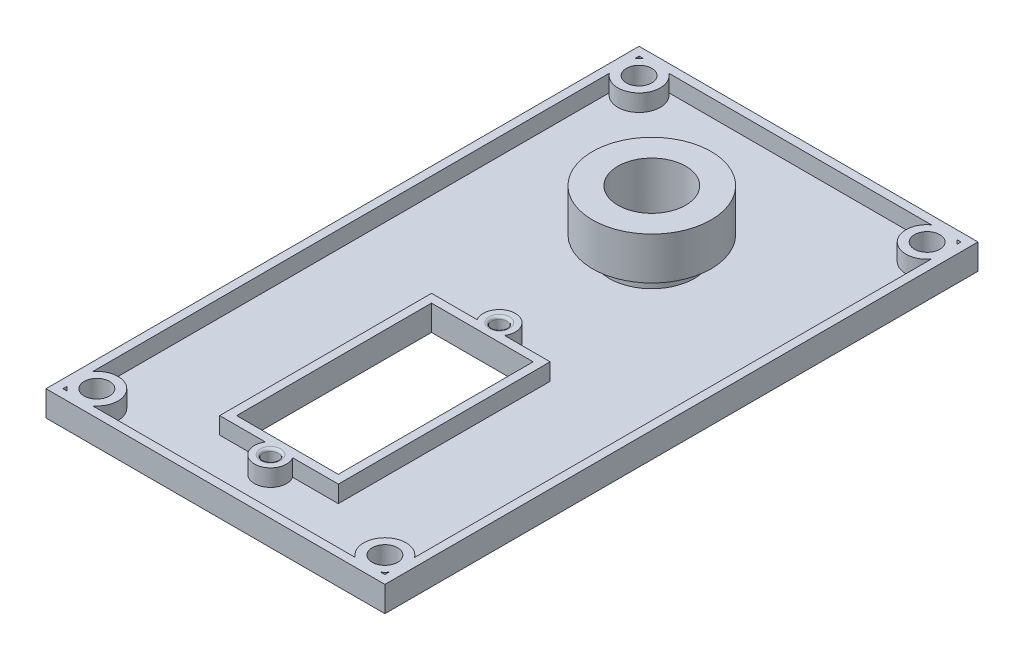
SolidWorks part; units mm, degrees
ref_plane "前视基准面" through (0, 0, 0) normal (0, 0, 1) x (1, 0, 0)
ref_plane "上视基准面" through (0, 0, 0) normal (0, 1, 0) x (1, 0, 0)
ref_plane "右视基准面" through (0, 0, 0) normal (1, 0, 0) x (0, 0, -1)
other "Configuration Table"
sketch "草图1" plane through (0, 0, 0) normal (0, 1, 0) x (1, 0, 0)
  line L0 (0, 38.6555) -> (0, -40.8509) construction
  line L1 (-20, 35) -> (20, 35)
  line L2 (-20, 35) -> (-20, -35)
  line L3 (-20, -35) -> (20, -35)
  line L4 (20, 35) -> (20, -35)
  line L5 (-20, 35) -> (20, -35) construction
  line L6 (-20, -35) -> (20, 35) construction
  line L8 (-6, -3.5) -> (6, -3.5)
  line L9 (-6, -3.5) -> (-6, -26.5)
  line L10 (-6, -26.5) -> (6, -26.5)
  line L11 (6, -3.5) -> (6, -26.5)
  line L12 (-6, -3.5) -> (6, -26.5) construction
  line L13 (-6, -26.5) -> (6, -3.5) construction
  point P0 (0, 0)
  point P8 (0, -15)
  dimension "D1" = 40
  dimension "D2" = 70
  dimension "D3" = 23
  dimension "D4" = 12
  dimension "D5" = 15
extrude "凸台-拉伸1" add sketch "草图1" along normal blind 3
sketch "草图2" plane through (0, 3, 0) normal (0, 1, 0) x (1, 0, 0)
  line L0 (0, 41.1406) -> (0, -42.4904) construction
  line L1 (-6, -26.5) -> (6, -26.5) construction
  line L2 (6, -3.5) -> (-6, -3.5) construction
  line L4 (20, -35) -> (20, 35)
  line L5 (20, 35) -> (-20, 35)
  line L6 (-20, 35) -> (-20, -35)
  line L7 (-20, -35) -> (20, -35)
  line L8 (20, -35) -> (20, 35)
  line L9 (20, 35) -> (-20, 35)
  line L10 (-20, 35) -> (-20, -35)
  line L11 (-20, -35) -> (20, -35)
  circle A0 centre (0, -28.5) radius 0.9
  circle A1 centre (0, -1.5) radius 0.9
  dimension "D2" = 1.8
  dimension "D3" = 1.8
  dimension "D4" = 2
  dimension "D5" = 2
  dimension "D1" = 0
extrude "切除-拉伸1" cut sketch "草图2" against normal blind 3 contours A0 | A1
sketch "草图3" plane through (0, 3, 0) normal (0, 1, 0) x (1, 0, 0)
  line L4 (20, -35) -> (20, 35)
  line L5 (20, 35) -> (-20, 35)
  line L6 (-20, 35) -> (-20, -35)
  line L7 (-20, -35) -> (20, -35)
  line L8 (20, -35) -> (20, 35)
  line L9 (20, 35) -> (-20, 35)
  line L10 (-20, 35) -> (-20, -35)
  line L11 (-20, -35) -> (20, -35)
  circle A0 centre (-17, -32) radius 1.5
  circle A1 centre (17, -32) radius 1.5
  circle A2 centre (17, 32) radius 1.5
  circle A3 centre (-17, 32) radius 1.5
  dimension "D2" = 3
  dimension "D3" = 3
  dimension "D4" = 3
  dimension "D5" = 3
  dimension "D6" = 3
  dimension "D7" = 3
  dimension "D8" = 3
  dimension "D9" = 3
  dimension "D10" = 3
  dimension "D11" = 3
  dimension "D12" = 3
  dimension "D13" = 3
  dimension "D1" = 0
extrude "切除-拉伸2" cut sketch "草图3" against normal through all contours A3 | A2 | A0 | A1 region at (-17, 3, 32) region at (17, 3, -32) region at (-17, 3, -32)
chamfer "倒角1" distance 0.5 angle 45 4 edges at (-17, 0, -30.5) (-17, 0, 33.5) (17, 0, 33.5) (17, 0, -30.5)
fillet "圆角1" radius 0.3 2 edges at (0, 3, 29.4) (0, 3, 2.4)
sketch "草图4" plane through (0, 0, 0) normal (0, -1, 0) x (1, 0, 0)
  line L0 (0, 49.5746) -> (0, -45.6466) construction
  line L1 (6, 3.5) -> (-6, 3.5) construction
  line L4 (20, -35) -> (20, 35)
  line L5 (20, 35) -> (-20, 35)
  line L6 (-20, 35) -> (-20, -35)
  line L7 (-20, -35) -> (20, -35)
  line L8 (20, -35) -> (20, 35)
  line L9 (20, 35) -> (-20, 35)
  line L10 (-20, 35) -> (-20, -35)
  line L11 (-20, -35) -> (20, -35)
  circle A0 centre (0, -16.5) radius 4
  dimension "D2" = 8
  dimension "D3" = 20
  dimension "D1" = 0
extrude "切除-拉伸3" cut sketch "草图4" against normal through all contours A0
sketch "草图5" plane through (0, 0, 0) normal (0, -1, 0) x (1, 0, 0)
  line L4 (20, -35) -> (20, 35)
  line L5 (20, 35) -> (-20, 35)
  line L6 (-20, 35) -> (-20, -35)
  line L7 (-20, -35) -> (20, -35)
  line L8 (20, -35) -> (20, 35)
  line L9 (20, 35) -> (-20, 35)
  line L10 (-20, 35) -> (-20, -35)
  line L11 (-20, -35) -> (20, -35)
  dimension "D1" = 0
sketch "草图6" plane through (0, 3, 0) normal (0, 1, 0) x (1, 0, 0)
  line L4 (20, -35) -> (20, 35)
  line L5 (20, 35) -> (-20, 35)
  line L6 (-20, 35) -> (-20, -35)
  line L7 (-20, -35) -> (20, -35)
  line L8 (20, -35) -> (20, 35)
  line L9 (20, 35) -> (-20, 35)
  line L10 (-20, 35) -> (-20, -35)
  line L11 (-20, -35) -> (20, -35)
  circle A0 centre (0, 16.5) radius 4
  dimension "D1" = 0
extrude "拉伸-薄壁1" add sketch "草图6" along normal blind 5 thin contours A0 thin type one direction wall 3
shell "抽壳1" thickness 1 removed face at (0, 3, 15)
